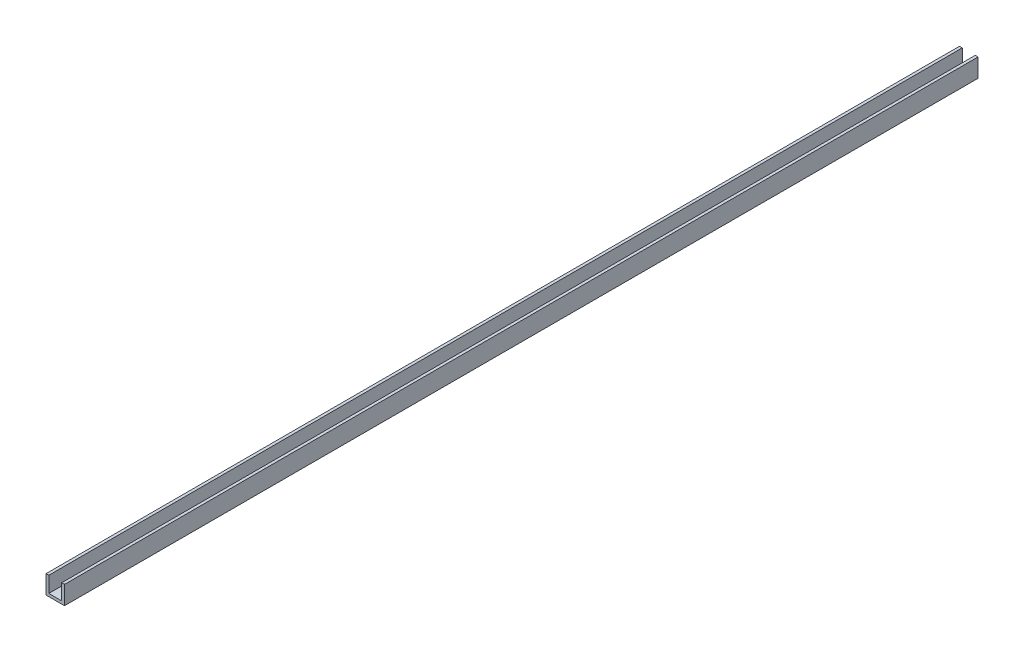
SolidWorks part; units mm, degrees
material "1060 Сплав"
ref_plane "Спереди" through (0, 0, 0) normal (0, 0, 1) x (1, 0, 0)
ref_plane "Сверху" through (0, 0, 0) normal (0, 1, 0) x (1, 0, 0)
ref_plane "Справа" through (0, 0, 0) normal (1, 0, 0) x (0, 0, -1)
sketch "Эскиз1" plane through (0, 0, 0) normal (0, 0, 1) x (1, 0, 0)
  line L0 (0, 0) -> (10, 0)
  line L1 (10, 0) -> (10, 10)
  line L2 (10, 10) -> (8.5, 10)
  line L3 (8.5, 10) -> (8.5, 1.5)
  line L4 (8.5, 1.5) -> (1.5, 1.5)
  line L5 (1.5, 1.5) -> (1.5, 10)
  line L6 (1.5, 10) -> (0, 10)
  line L7 (0, 10) -> (0, 0)
  dimension "D1" = 1.5
  dimension "D2" = 1.5
  dimension "D3" = 10
extrude "Бобышка-Вытянуть1" add sketch "Эскиз1" along normal blind 493
sketch "Эскиз2" plane through (10, 0, 0) normal (1, 0, 0) x (0, 0, -1)
  line L0 (-493, 5) -> (0, 5) construction
  line L1 (-493, 0) -> (-493, 10) construction
  line L2 (0, 0) -> (0, 10) construction
ref_axis "Ось1" through (5, 0, 493) along (0, 0, -1)
equation "\"ATX.Case.01.Dimension.1\"=499"
equation "\"ATX.Case.01.Profile.20.Width\"=20"
equation "\"ATX.Case.01.Profile.20.Thickness\" = 1.5"
equation "\"ATX.Case.01.Profile.10.Width\"=10"
equation "\"ATX.Case.01.Profile.10.Thickness\"=1.5"
equation "\"D2@Эскиз1\"= \"ATX.Case.01.Profile.10.Thickness\""
equation "\"D1@Эскиз1\"= \"ATX.Case.01.Profile.10.Thickness\""
equation "\"D3@Эскиз1\"= \"ATX.Case.01.Profile.10.Width\""
equation "\"D1@Бобышка-Вытянуть1\"= \"ATX.Case.01.Dimension.1\" - \"ATX.Case.01.Profile.20.Thickness\" * 2 * 2"
